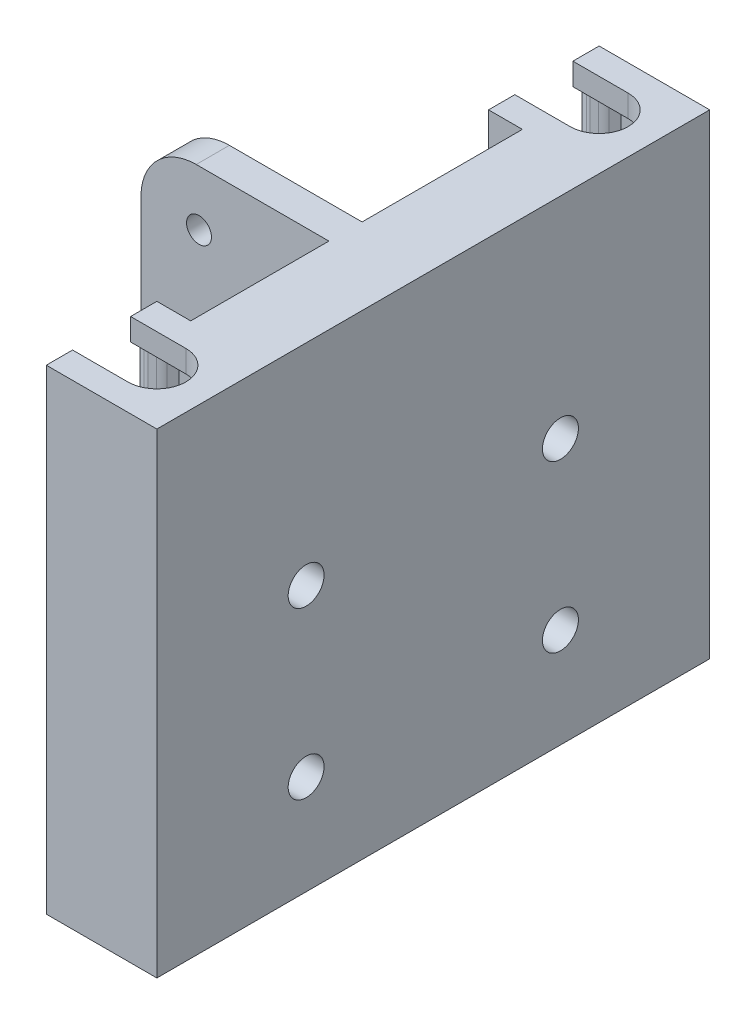
SolidWorks part; units mm, degrees
ref_plane "Front Plane" through (0, 0, 0) normal (0, 0, 1) x (1, 0, 0)
ref_plane "Top Plane" through (0, 0, 0) normal (0, 1, 0) x (1, 0, 0)
ref_plane "Right Plane" through (0, 0, 0) normal (1, 0, 0) x (0, 0, -1)
sketch "Sketch1" plane through (0, 0, 0) normal (0, 1, 0) x (1, 0, 0)
  line L21 (-7.527, -41.3041) -> (-7.527, 58.6959)
  line L22 (-7.527, 58.6959) -> (-27.527, 58.6959)
  line L23 (-27.527, 58.6959) -> (-27.527, 38.6959)
  line L24 (-27.527, 38.6959) -> (-21.4063, 38.6959)
  line L25 (-21.4063, 38.6959) -> (-21.4063, -21.3041)
  line L26 (-21.4063, -21.3041) -> (-27.527, -21.3041)
  line L27 (-27.527, -21.3041) -> (-27.527, -41.3041)
  line L28 (-27.527, -41.3041) -> (-7.527, -41.3041)
extrude "Boss-Extrude1" add sketch "Sketch1" along normal blind 86
sketch "Sketch2" plane through (0, 86, 0) normal (0, 1, 0) x (1, 0, 0)
  line L0 (-17.527, 53.9459) -> (-27.527, 53.9459)
  line L1 (-27.527, 58.6959) -> (-27.527, 38.6959) construction
  line L2 (-17.527, 43.4459) -> (-27.527, 43.4459)
  line L3 (-27.527, 53.9459) -> (-27.527, 43.4459)
  line L4 (-17.527, -26.0541) -> (-27.527, -26.0541)
  line L5 (-27.527, -21.3041) -> (-27.527, -41.3041) construction
  line L6 (-27.527, -26.0541) -> (-27.527, -36.5541)
  line L7 (-27.527, -36.5541) -> (-17.527, -36.5541)
  arc A2 (-17.527, -36.5541) -> (-17.527, -26.0541) centre (-17.527, -31.3041) ccw
  arc A3 (-17.527, 43.4459) -> (-17.527, 53.9459) centre (-17.527, 48.6959) ccw
  dimension "D1" = 10.5
  dimension "D2" = 10.5
extrude "Cut-Extrude1" cut sketch "Sketch2" against normal up to next
sketch "Sketch3" plane through (-27.527, 0, 0) normal (-1, 0, 0) x (0, 0, 1)
  line L0 (41.3041, 73.5608) -> (-72.5469, 73.5608) construction
  line L1 (41.3041, 86) -> (41.3041, 0) construction
  line L2 (41.3041, 8.3895) -> (-72.5469, 8.3895) construction
  line L3 (31.3041, 0) -> (31.3041, 89.0163) construction
  line L4 (26.0541, 0) -> (36.5541, 0) construction
  line L5 (-48.6959, 0) -> (-48.6959, 89.0163) construction
  line L6 (-53.9459, 0) -> (-43.4459, 0) construction
  line L8 (38.8041, 8.3895) -> (23.8041, 8.3895)
  line L9 (38.8041, 8.3895) -> (38.8041, 25.5895)
  line L10 (38.8041, 25.5895) -> (23.8041, 25.5895)
  line L11 (23.8041, 8.3895) -> (23.8041, 25.5895)
  point P18 (31.3041, 8.3895)
  dimension "D1" = 15
  dimension "D2" = 17.2
sketch "Sketch4" plane through (0, 0, 0) normal (0, -1, 0) x (1, 0, 0)
  line L0 (-27.527, 24.3841) -> (-27.527, 38.2241)
  line L1 (-21.057, -56.2159) -> (-17.527, -56.2159)
  line L2 (-27.527, -48.6959) -> (-17.527, -48.6959) construction
  line L3 (-27.527, 31.3041) -> (-7.2627, 31.3041) construction
  line L4 (-21.057, -41.1759) -> (-17.527, -41.1759)
  line L5 (-27.527, 41.3041) -> (-22.1398, 41.3041) construction
  line L7 (-21.057, 23.7841) -> (-17.527, 23.7841)
  line L8 (-21.057, 38.8241) -> (-17.527, 38.8241)
  line L9 (-27.527, -55.6159) -> (-27.527, -41.7759)
  line L10 (-27.527, -55.6159) -> (-25.9493, -54.8271)
  line L20 (-27.527, 38.2241) -> (-25.9493, 37.4352)
  line L21 (-25.0549, 37.2241) -> (-23.5502, 37.2241)
  line L22 (-22.1794, 37.7677) -> (-21.057, 38.8241)
  line L23 (-27.527, 24.3841) -> (-25.9493, 25.1729)
  line L24 (-25.0549, 25.3841) -> (-23.5502, 25.3841)
  line L25 (-22.1794, 24.8405) -> (-21.057, 23.7841)
  line L26 (-25.0549, -54.6159) -> (-23.5502, -54.6159)
  line L27 (-22.1794, -55.1595) -> (-21.057, -56.2159)
  line L28 (-27.527, -41.7759) -> (-25.9493, -42.5648)
  line L29 (-25.0549, -42.7759) -> (-23.5502, -42.7759)
  line L30 (-22.1794, -42.2323) -> (-21.057, -41.1759)
  line L31 (-27.527, 41.3041) -> (-27.527, -72.5469) construction
  arc A1 (-17.527, 23.7841) -> (-17.527, 38.8241) centre (-17.527, 31.3041) ccw
  arc A6 (-25.9493, 37.4352) -> (-25.0549, 37.2241) centre (-25.0549, 39.2241) ccw
  arc A7 (-23.5502, 37.2241) -> (-22.1794, 37.7677) centre (-23.5502, 39.2241) ccw
  arc A8 (-23.5502, 25.3841) -> (-22.1794, 24.8405) centre (-23.5502, 23.3841) cw
  arc A9 (-25.9493, 25.1729) -> (-25.0549, 25.3841) centre (-25.0549, 23.3841) cw
  arc A11 (-17.527, -56.2159) -> (-17.527, -41.1759) centre (-17.527, -48.6959) ccw
  arc A12 (-25.9493, -42.5648) -> (-25.0549, -42.7759) centre (-25.0549, -40.7759) ccw
  arc A13 (-23.5502, -42.7759) -> (-22.1794, -42.2323) centre (-23.5502, -40.7759) ccw
  arc A14 (-23.5502, -54.6159) -> (-22.1794, -55.1595) centre (-23.5502, -56.6159) cw
  arc A15 (-25.9493, -54.8271) -> (-25.0549, -54.6159) centre (-25.0549, -56.6159) cw
  point P5 (0, 0)
  point P29 (-25.527, -42.7759)
  point P32 (-22.757, -42.7759)
  point P35 (-22.757, -54.6159)
  point P38 (-25.527, -54.6159)
  point P55 (-25.527, 37.2241)
  point P58 (-22.757, 37.2241)
  point P61 (-22.757, 25.3841)
  point P64 (-25.527, 25.3841)
  dimension "D10" = 1.6
  dimension "D25" = 2
  dimension "D15" = 2
  dimension "D3" = 7.52
  dimension "D4" = 7.52
  dimension "D6" = 1.6
  dimension "D7" = 2
  dimension "D9" = 2
  dimension "D11" = 2.77
  dimension "D12" = 2.77
  dimension "D13" = 1.7
  dimension "D14" = 1.7
  dimension "D17" = 1.6
  dimension "D18" = 1.6
  dimension "D19" = 2
  dimension "D20" = 2
  dimension "D21" = 2.77
  dimension "D22" = 2.77
  dimension "D23" = 1.7
  dimension "D24" = 1.7
extrude "Cut-Extrude2" cut sketch "Sketch4" against normal blind 17.2 from offset 4 offset against normal yes
extrude "Cut-Extrude3" cut sketch "Sketch4<2>" against normal blind 17 from offset 65 offset against normal yes
sketch "Sketch4<2>" plane through (0, 0, 0) normal (0, -1, 0) x (1, 0, 0) same geometry as "Sketch4"
sketch "Sketch5" plane through (-21.4063, 0, 0) normal (1, 0, 0) x (0, 0, -1)
  line L1 (9.6959, 86) -> (-2.3041, 86)
  line L2 (9.6959, 86) -> (9.6959, 15)
  line L3 (9.6959, 15) -> (-2.3041, 15)
  line L4 (-2.3041, 86) -> (-2.3041, 15)
  line L6 (-41.3041, 86) -> (-41.3041, 0) construction
  line L9 (38.6959, 0) -> (-21.3041, 0) construction
  line L10 (38.6959, 86) -> (-21.3041, 86) construction
  dimension "D1" = 12
  dimension "D2" = 39
  dimension "D4" = 15
extrude "Boss-Extrude2" add sketch "Sketch5" against normal blind 34
sketch "Sketch6" plane through (-55.4063, 0, 0) normal (-1, 0, 0) x (0, 0, 1)
  line L0 (2.3041, 15) -> (-9.6959, 15) construction
  line L1 (-3.6959, 15) -> (2.3041, 15)
  line L2 (-3.6959, 15) -> (-3.6959, 86)
  line L3 (-3.6959, 86) -> (2.3041, 86)
  line L4 (2.3041, 15) -> (2.3041, 86)
  line L5 (-9.6959, 86) -> (2.3041, 86) construction
  line L6 (2.3041, 86) -> (2.3041, 15) construction
extrude "Cut-Extrude4" cut sketch "Sketch6" against normal up to surface (34 mm away) up to face at (-21.4063, 46.75, -6.1959)
sketch "Sketch8" plane through (0, 0, -3.6959) normal (0, 0, 1) x (1, 0, 0)
  line L0 (-44.9063, 86) -> (-44.9063, 0) construction
  line L1 (-21.4063, 86) -> (-21.4063, 15) construction
  line L4 (-21.4063, 86) -> (-55.4063, 86) construction
  line L5 (-44.9063, 25) -> (-20.4369, 25) construction
  line L6 (-27.9063, 88.1256) -> (-27.9063, 8.6291) construction
  line L7 (-44.9063, 76) -> (-28.0234, 76) construction
  line L8 (-21.4063, 15) -> (-55.4063, 15) construction
  circle A1 centre (-44.9063, 25) radius 2.25
  circle A2 centre (-44.9063, 76) radius 2.25
  circle A3 centre (-27.9063, 25) radius 2.25
  circle A4 centre (-27.9063, 76) radius 2.25
  dimension "D2" = 4.5
  dimension "D4" = 4.5
  dimension "D5" = 4.5
  dimension "D1" = 10
  dimension "D3" = 10
  dimension "D6" = 6.5
  dimension "D7" = 17
extrude "Cut-Extrude6" cut sketch "Sketch8" against normal up to next
sketch "Sketch9" plane through (-7.527, 0, 0) normal (1, 0, 0) x (0, 0, -1)
  line L0 (-14.3041, 86) -> (-14.3041, 0) construction
  line L1 (-41.3041, 86) -> (58.6959, 86) construction
  line L2 (-41.3041, 0) -> (58.6959, 0) construction
  line L3 (-41.3041, 86) -> (-41.3041, 0) construction
  line L4 (31.6959, 86) -> (31.6959, 0) construction
  line L5 (-41.3041, 86) -> (58.6959, 86) construction
  line L6 (58.6959, 86) -> (58.6959, 0) construction
  circle A0 centre (-14.3041, 48) radius 3.25
  circle A1 centre (-14.3041, 18) radius 3.25
  circle A2 centre (31.6959, 48) radius 3.25
  circle A3 centre (31.6959, 18) radius 3.25
  dimension "D2" = 6.5
  dimension "D3" = 6.5
  dimension "D7" = 6.5
  dimension "D8" = 6.5
  dimension "D1" = 27
  dimension "D4" = 38
  dimension "D5" = 30
  dimension "D6" = 27
extrude "Cut-Extrude7" cut sketch "Sketch9" against normal through all
sketch "Sketch10" plane through (0, 0, -9.6959) normal (0, 0, -1) x (-1, 0, 0)
  line L1 (48.4063, 27.0207) -> (44.9063, 29.0415)
  line L2 (44.9063, 29.0415) -> (41.4063, 27.0207)
  line L3 (41.4063, 27.0207) -> (41.4063, 22.9793)
  line L4 (41.4063, 22.9793) -> (44.9063, 20.9585)
  line L5 (44.9063, 20.9585) -> (48.4063, 22.9793)
  line L6 (48.4063, 22.9793) -> (48.4063, 27.0207)
  line L7 (48.4063, 78.0207) -> (44.9063, 80.0415)
  line L8 (44.9063, 80.0415) -> (41.4063, 78.0207)
  line L9 (41.4063, 78.0207) -> (41.4063, 73.9793)
  line L10 (41.4063, 73.9793) -> (44.9063, 71.9585)
  line L11 (44.9063, 71.9585) -> (48.4063, 73.9793)
  line L12 (48.4063, 73.9793) -> (48.4063, 78.0207)
  line L13 (7.527, 0) -> (7.527, 86) construction
  line L14 (24.4063, 22.9793) -> (27.9063, 20.9585)
  line L15 (27.9063, 20.9585) -> (31.4063, 22.9793)
  line L16 (31.4063, 22.9793) -> (31.4063, 27.0207)
  line L17 (31.4063, 27.0207) -> (27.9063, 29.0415)
  line L18 (27.9063, 29.0415) -> (24.4063, 27.0207)
  line L19 (24.4063, 27.0207) -> (24.4063, 22.9793)
  line L20 (21.4063, 15) -> (21.4063, 86) construction
  line L22 (27.796, 71.9601) -> (31.3498, 73.8845)
  line L23 (31.3498, 73.8845) -> (31.4602, 77.9244)
  line L24 (31.4602, 77.9244) -> (28.0166, 80.0399)
  line L25 (28.0166, 80.0399) -> (24.4628, 78.1155)
  line L26 (24.4628, 78.1155) -> (24.3524, 74.0756)
  line L27 (24.3524, 74.0756) -> (27.796, 71.9601)
  circle A0 centre (44.9063, 25) radius 3.5 construction
  circle A1 centre (44.9063, 76) radius 3.5 construction
  circle A2 centre (44.9063, 76) radius 2.25 construction
  circle A3 centre (27.9063, 25) radius 3.5 construction
  circle A4 centre (27.9063, 76) radius 3.5 construction
  circle A5 centre (27.9063, 76) radius 2.25 construction
  point P20 (24.4063, 25)
  dimension "D1" = 7
  dimension "D2" = 7
  dimension "D3" = 7
  dimension "D4" = 7
extrude "Cut-Extrude8" cut sketch "Sketch10" against normal blind 2.5
fillet "Fillet1" radius 10 2 edges at (-55.4063, 86, -6.6959) (-55.4063, 15, -6.6959)
